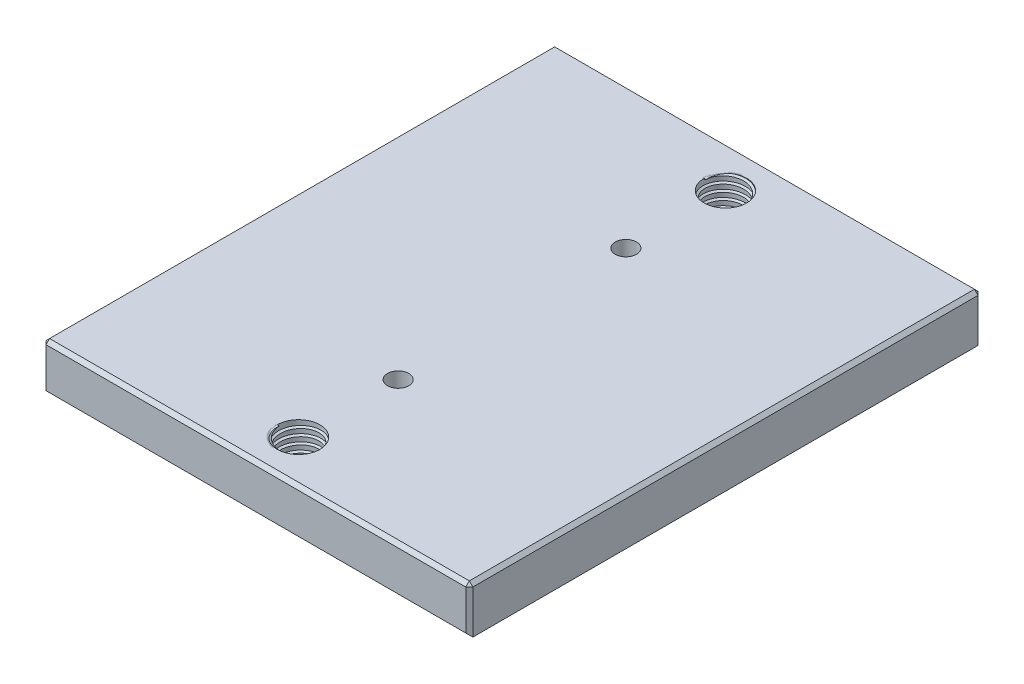
SolidWorks part; units mm, degrees
ref_plane "Front Plane" through (0, 0, 0) normal (0, 0, 1) x (1, 0, 0)
ref_plane "Top Plane" through (0, 0, 0) normal (0, 1, 0) x (1, 0, 0)
ref_plane "Right Plane" through (0, 0, 0) normal (1, 0, 0) x (0, 0, -1)
other "Configuration Table"
sketch "草图1" plane through (0, 0, 0) normal (0, 1, 0) x (1, 0, 0)
  line L1 (-30, 36) -> (30, 36)
  line L2 (-30, 36) -> (-30, -36)
  line L3 (-30, -36) -> (30, -36)
  line L4 (30, 36) -> (30, -36)
  line L5 (-30, 36) -> (30, -36) construction
  line L6 (-30, -36) -> (30, 36) construction
  point P0 (0, 0)
  dimension "D1" = 72
  dimension "D2" = 60
extrude "凸台-拉伸1" add sketch "草图1" along normal blind 6.6
sketch "草图2" plane through (0, 6.6, 0) normal (0, 1, 0) x (1, 0, 0)
  line L0 (0, 0) -> (0, 16) construction
  circle A0 centre (0, 16) radius 1.5
  dimension "D2" = 3
  dimension "D1" = 16
extrude "切除-拉伸1" cut sketch "草图2" against normal blind 6.6
mirror "镜向1" about plane through (0, 0, 0) normal (0, 0, 1) of "切除-拉伸1"
sketch "草图3" plane through (0, 6.6, 0) normal (0, 1, 0) x (1, 0, 0)
  line L0 (0, 0) -> (0, 30) construction
  circle A0 centre (0, 30) radius 3
  dimension "D2" = 6
  dimension "D1" = 30
extrude "切除-拉伸2" cut sketch "草图3" against normal blind 6.6
sketch "草图4" plane through (0, 6.6, 0) normal (0, 1, 0) x (1, 0, 0)
  circle A0 centre (0, 30) radius 3 construction
  circle A1 centre (0, 30) radius 3
curve "螺旋线/涡状线1" pitch 1 height 6 radius 3 centre (0, 6.6, -30) axis (0, -1, 0) start towards (0, 0, 1)
ref_axis "基准轴1" through (0, 0, -30) along (0, 1, 0)
ref_plane "基准面1" through (0, 0, -30) normal (0, 0, 1) x (1, 0, 0)
sketch "草图5" plane through (0, 0, -30) normal (0, 0, 1) x (1, 0, 0)
  line L1 (-2.7113, 6.6) -> (-3.1443, 6.85)
  line L2 (-3.1443, 6.85) -> (-3.1443, 6.35)
  line L3 (-3.1443, 6.35) -> (-2.7113, 6.6)
  circle A0 centre (-3, 6.6) radius 0.1443 construction
  spline S0 degree 3 poles (-3, 6.6) (-3, 6.5793) (-2.8438, 6.5374) (-2.1765, 6.475) (-1.1779, 6.4125) (0, 6.35) (1.1779, 6.2875) (2.1765, 6.225) (2.8438, 6.1625) (3.0781, 6.1) (2.8438, 6.0375) (2.1765, 5.975) (0.8451, 5.8917) (-0.8451, 5.8083) (-2.1765, 5.725) (-2.8438, 5.6625) (-3.0781, 5.6) (-2.8438, 5.5375) (-2.1765, 5.475) (-0.8451, 5.3917) (0.8451, 5.3083) (2.1765, 5.225) (2.8438, 5.1625) (3.0781, 5.1) (2.8438, 5.0375) (2.1765, 4.975) (0.8451, 4.8917) (-0.8451, 4.8083) (-2.1765, 4.725) (-2.8438, 4.6625) (-3.0781, 4.6) (-2.8438, 4.5375) (-2.1765, 4.475) (-0.8451, 4.3917) (0.8451, 4.3083) (2.1765, 4.225) (2.8438, 4.1625) (3.0781, 4.1) (2.8438, 4.0375) (2.1765, 3.975) (0.8451, 3.8917) (-0.8451, 3.8083) (-2.1765, 3.725) (-2.8438, 3.6625) (-3.0781, 3.6) (-2.8438, 3.5375) (-2.1765, 3.475) (-0.8451, 3.3917) (0.8451, 3.3083) (2.1765, 3.225) (2.8438, 3.1625) (3.0781, 3.1) (2.8438, 3.0375) (2.1765, 2.975) (0.8451, 2.8917) (-0.8451, 2.8083) (-2.1765, 2.725) (-2.8438, 2.6625) (-3.0781, 2.6) (-2.8438, 2.5375) (-2.1765, 2.475) (-0.8451, 2.3917) (0.8451, 2.3083) (2.1765, 2.225) (2.8438, 2.1625) (3.0781, 2.1) (2.8438, 2.0375) (2.1765, 1.975) (0.8451, 1.8917) (-0.8451, 1.8083) (-2.1765, 1.725) (-2.8438, 1.6625) (-3.0781, 1.6) (-2.8438, 1.5375) (-2.1765, 1.475) (-0.8451, 1.3917) (0.8451, 1.3083) (2.1765, 1.225) (2.8438, 1.1625) (3.0781, 1.1) (2.8438, 1.0375) (2.1765, 0.975) (1.1779, 0.9125) (0, 0.85) (-1.1779, 0.7875) (-2.1765, 0.725) (-2.8438, 0.6626) (-3, 0.6207) (-3, 0.6) knots 0 0 0 0 0.010417 0.020833 0.03125 0.041667 0.052083 0.0625 0.072917 0.083333 0.09375 0.104167 0.114583 0.135417 0.145833 0.15625 0.166667 0.177083 0.1875 0.197917 0.21875 0.229167 0.239583 0.25 0.260417 0.270833 0.28125 0.302083 0.3125 0.322917 0.333333 0.34375 0.354167 0.364583 0.385417 0.395833 0.40625 0.416667 0.427083 0.4375 0.447917 0.46875 0.479167 0.489583 0.5 0.510417 0.520833 0.53125 0.552083 0.5625 0.572917 0.583333 0.59375 0.604167 0.614583 0.635417 0.645833 0.65625 0.666667 0.677083 0.6875 0.697917 0.71875 0.729167 0.739583 0.75 0.760417 0.770833 0.78125 0.802083 0.8125 0.822917 0.833333 0.84375 0.854167 0.864583 0.885417 0.895833 0.90625 0.916667 0.927083 0.9375 0.947917 0.958333 0.96875 0.979167 0.989583 1 1 1 1 construction
  dimension "D1" = 0.5
sweep "扫描1" add profiles "草图5" path "螺旋线/涡状线1"
mirror "镜向2" about plane through (0, 0, 0) normal (0, 0, 1) of bodies 105
mirror "镜向4" about plane through (0, 0, 0) normal (0, 0, 1) of "切除-拉伸2"
sketch "草图6" plane through (0, 0, 36) normal (0, 0, 1) x (1, 0, 0)
  line L1 (-30, 6.6) -> (30, 6.6)
  line L2 (-30, 6.6) -> (-30, 11.5309)
  line L3 (-30, 11.5309) -> (30, 11.5309)
  line L4 (-30, 0) -> (30, 0)
  line L5 (30, 0) -> (30, 6.6)
  line L6 (30, 6.6) -> (-30, 6.6)
  line L7 (-30, 6.6) -> (-30, 0)
  line L8 (-30, 0) -> (30, 0) construction
  line L9 (30, 0) -> (30, 6.6) construction
  line L10 (30, 6.6) -> (-30, 6.6) construction
  line L11 (-30, 6.6) -> (-30, 0) construction
  line L12 (30, 6.6) -> (30, 11.5309)
  dimension "D1" = 0
extrude "切除-拉伸3" cut sketch "草图6" against normal blind 70
chamfer "倒角1" distance 0.5 angle 45 11 edges at (30, 3.3, -36) (0, 6.6, -36) (0, 0, -36) (0, 6.6, 36) (-30, 3.3, -36) (-30, 6.6, 0) (-30, 3.3, 36) (-30, 0, 0) (0, 0, 36) (30, 3.3, 36) (30, 6.6, 0)
